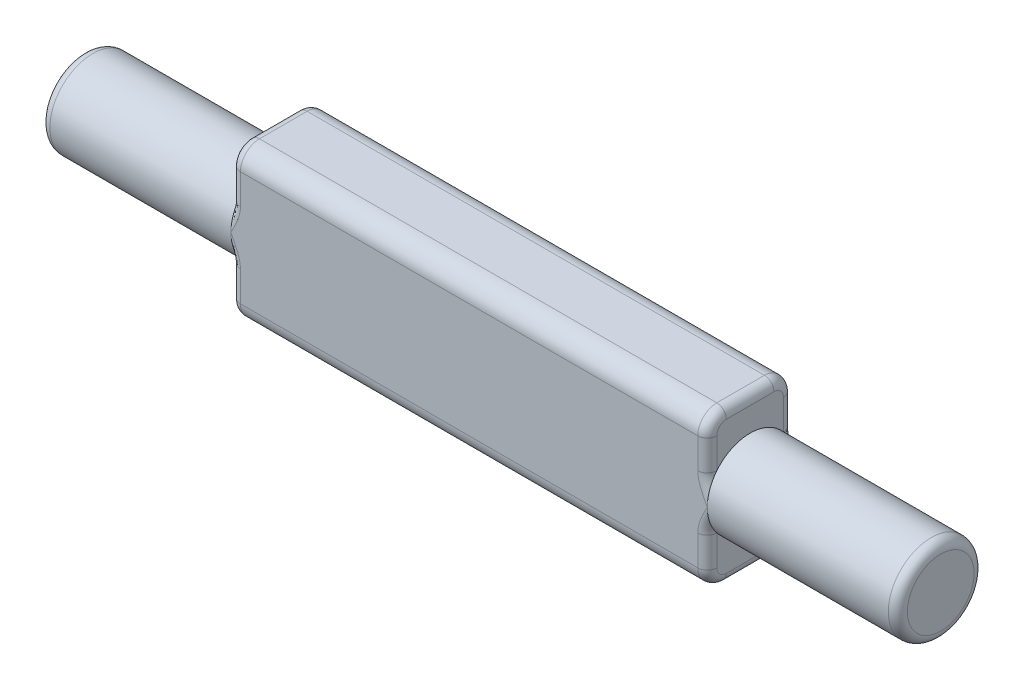
SolidWorks part; units mm, degrees
ref_plane "Front Plane" through (0, 0, 0) normal (0, 0, 1) x (1, 0, 0)
ref_plane "Top Plane" through (0, 0, 0) normal (0, 1, 0) x (1, 0, 0)
ref_plane "Right Plane" through (0, 0, 0) normal (1, 0, 0) x (0, 0, -1)
sketch "Sketch1" plane through (0, 0, 0) normal (1, 0, 0) x (0, 0, -1)
  line L1 (-2.25, -4) -> (2.25, -4)
  line L2 (-2.25, -4) -> (-2.25, 4)
  line L3 (-2.25, 4) -> (2.25, 4)
  line L4 (2.25, -4) -> (2.25, 4)
  line L5 (-2.25, -4) -> (2.25, 4) construction
  line L6 (-2.25, 4) -> (2.25, -4) construction
  circle A0 centre (0, 0) radius 2.25
  dimension "D1" = 4.5
  dimension "D2" = 8
extrude "Boss-Extrude1" add sketch "Sketch1" along normal blind 10 contours A0
extrude "Boss-Extrude2" add sketch "Sketch1<3>" against normal blind 25 contours L3 L4 L1 L2
sketch "Sketch1<3>" plane through (0, 0, 0) normal (1, 0, 0) x (0, 0, -1) same geometry as "Sketch1"
extrude "Boss-Extrude3" add sketch "Sketch1<4>" against normal blind 10 from vertex contours A0 region at (0, 0, 0) starting at point (-25, 4, -2.25)
sketch "Sketch1<4>" plane through (0, 0, 0) normal (1, 0, 0) x (0, 0, -1) same geometry as "Sketch1"
fillet "Fillet1" radius 0.5 2 edges at (10, 0, -2.25) (-35, 0, -2.25)
fillet "Fillet2" radius 1 4 edges at (-12.5, -4, -2.25) (-12.5, -4, 2.25) (-12.5, 4, 2.25) (-12.5, 4, -2.25)
fillet "Fillet3" radius 0.5 20 edges at (-25, 3.7071, 1.9571) (-25, 1.5, 2.25) (-25, -1.5, 2.25) (-25, -3.7071, 1.9571) (-25, -4, 0) (-25, -3.7071, -1.9571) (-25, -1.5, -2.25) (-25, 1.5, -2.25) (-25, 3.7071, -1.9571) (0, 3.7071, 1.9571) (0, 1.5, 2.25) (0, -1.5, 2.25) (0, -3.7071, 1.9571) (0, -4, 0) (0, -3.7071, -1.9571) (0, -1.5, -2.25) (0, 1.5, -2.25) (0, 3.7071, -1.9571) (-25, 4, 0) (0, 4, 0)
